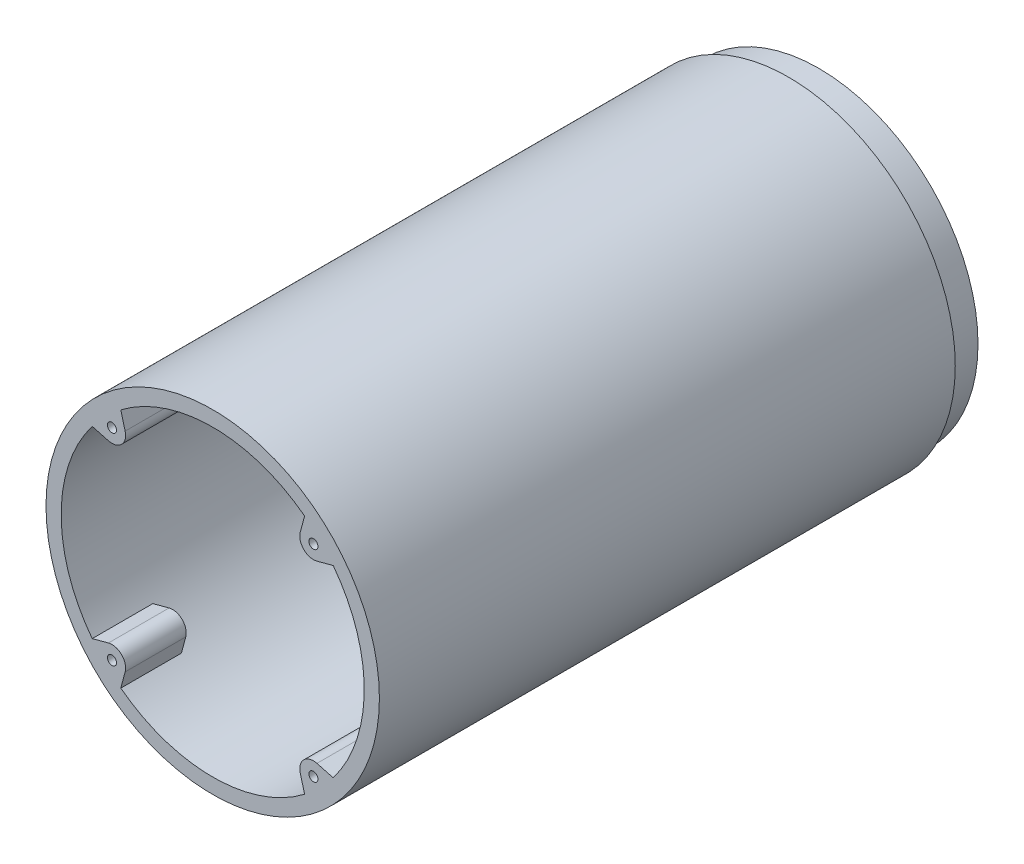
SolidWorks part; units mm, degrees
material "ABS"
ref_plane "前视基准面" through (0, 0, 0) normal (0, 0, 1) x (1, 0, 0)
ref_plane "上视基准面" through (0, 0, 0) normal (0, 1, 0) x (1, 0, 0)
ref_plane "右视基准面" through (0, 0, 0) normal (1, 0, 0) x (0, 0, -1)
sketch "草图2" plane through (0, 0, 0) normal (0, 0, 1) x (1, 0, 0)
  circle A0 centre (0, 0) radius 55
  circle A1 centre (0, 0) radius 50
  dimension "D1" = 100
  dimension "D2" = 110
extrude "凸台-拉伸1" add sketch "草图2" along normal blind 200
sketch "草图1" plane through (0, 0, 0) normal (0, 0, 1) x (1, 0, 0)
  line L0 (0, 0) -> (-25.5751, 0) construction
  line L1 (-49.5531, 6.6702) -> (-44.75, 3.8971)
  line L2 (-49.5531, -6.6702) -> (-44.75, -3.8971)
  line L3 (0, 0) -> (-6.6702, 49.5531) construction
  line L4 (-49.5531, -6.6702) -> (0, 0) construction
  line L5 (6.6702, 49.5531) -> (3.8971, 44.75)
  line L6 (-6.6702, 49.5531) -> (-3.8971, 44.75)
  line L7 (49.5531, -6.6702) -> (44.75, -3.8971)
  line L8 (49.5531, 6.6702) -> (44.75, 3.8971)
  line L9 (-6.6702, -49.5531) -> (-3.8971, -44.75)
  line L10 (6.6702, -49.5531) -> (3.8971, -44.75)
  circle A0 centre (0, 0) radius 50 construction
  circle A1 centre (0, 0) radius 55
  circle A2 centre (-47, 0) radius 1.5
  arc A4 (-44.75, 3.8971) -> (-44.75, -3.8971) centre (-47, 0) cw
  arc A5 (-49.5531, 6.6702) -> (-6.6702, 49.5531) centre (0, 0) cw
  circle A6 centre (0, 47) radius 1.5
  arc A7 (3.8971, 44.75) -> (-3.8971, 44.75) centre (0, 47) cw
  arc A8 (6.6702, 49.5531) -> (49.5531, 6.6702) centre (0, 0) cw
  circle A9 centre (47, 0) radius 1.5
  arc A10 (44.75, -3.8971) -> (44.75, 3.8971) centre (47, 0) cw
  arc A11 (49.5531, -6.6702) -> (6.6702, -49.5531) centre (0, 0) cw
  circle A12 centre (0, -47) radius 1.5
  arc A13 (-3.8971, -44.75) -> (3.8971, -44.75) centre (0, -47) cw
  arc A14 (-6.6702, -49.5531) -> (-49.5531, -6.6702) centre (0, 0) cw
  circle A15 centre (0, 0) radius 50 construction
  circle A16 centre (0, 0) radius 55 construction
  point P38 (0, 0)
  dimension "D3" = 47
  dimension "D4" = 3
  dimension "D5" = 3
  dimension "D7" = 90
  dimension "D8" = 4
  dimension "D6" = 30
extrude "凸台-拉伸2" add sketch "草图1" along normal blind 20 contours A1 A12 A9 A6 A2 L9 A14 L2 A4 L1 A5 L6 A7 L5 A8 L8 A10 L7 A11 L10 A13 region at (-53.4444, 0, 0)
sketch "草图3" plane through (0, 0, 20) normal (0, 0, 1) x (1, 0, 0)
  line L0 (-1.5877, 44.25) -> (1.5877, 44.25)
  line L1 (-44.25, -1.5877) -> (-44.25, 1.5877)
  line L2 (-44.25, 1.5877) -> (-47, 3.1754)
  line L3 (-47, 3.1754) -> (-49.75, 1.5877)
  line L4 (-49.75, 1.5877) -> (-49.75, -1.5877)
  line L5 (-49.75, -1.5877) -> (-47, -3.1754)
  line L6 (-47, -3.1754) -> (-44.25, -1.5877)
  line L7 (1.5877, 44.25) -> (3.1754, 47)
  line L8 (3.1754, 47) -> (1.5877, 49.75)
  line L9 (1.5877, 49.75) -> (-1.5877, 49.75)
  line L10 (-1.5877, 49.75) -> (-3.1754, 47)
  line L11 (-3.1754, 47) -> (-1.5877, 44.25)
  line L12 (44.25, 1.5877) -> (44.25, -1.5877)
  line L13 (44.25, -1.5877) -> (47, -3.1754)
  line L14 (47, -3.1754) -> (49.75, -1.5877)
  line L15 (49.75, -1.5877) -> (49.75, 1.5877)
  line L16 (49.75, 1.5877) -> (47, 3.1754)
  line L17 (47, 3.1754) -> (44.25, 1.5877)
  line L18 (1.5877, -44.25) -> (-1.5877, -44.25)
  line L19 (-1.5877, -44.25) -> (-3.1754, -47)
  line L20 (-3.1754, -47) -> (-1.5877, -49.75)
  line L21 (-1.5877, -49.75) -> (1.5877, -49.75)
  line L22 (1.5877, -49.75) -> (3.1754, -47)
  line L23 (3.1754, -47) -> (1.5877, -44.25)
  circle A0 centre (-47, 0) radius 2.75 construction
  circle A1 centre (0, 47) radius 2.75 construction
  circle A2 centre (47, 0) radius 2.75 construction
  circle A3 centre (0, -47) radius 2.75 construction
  point P36 (0, 0)
  dimension "D1" = 5.5
  dimension "D2" = 4
extrude "切除-拉伸1" cut sketch "草图3" against normal blind 2
ref_plane "基准面4" through (0, 0, 100) normal (0, 0, -1) x (-1, 0, 0)
sketch "草图4" plane through (0, 0, 0) normal (0, 0, -1) x (-1, 0, 0)
  circle A0 centre (0, 0) radius 55
  circle A1 centre (0, 0) radius 52.5
  circle A2 centre (0, 0) radius 55 construction
  dimension "D1" = 2.5
extrude "切除-拉伸2" cut sketch "草图4" against normal blind 10
sketch "草图5" plane through (0, 0, 0) normal (0, 0, 1) x (1, 0, 0)
  line L0 (0, 0) -> (-16.1279, 16.1279) construction
  line L1 (-30.3228, 39.7559) -> (-28.8874, 34.3987)
  line L2 (-39.7559, 30.3228) -> (-34.3987, 28.8874)
  line L3 (0, 0) -> (30.3228, 39.7559) construction
  line L4 (-39.7559, 30.3228) -> (0, 0) construction
  line L5 (39.7559, 30.3228) -> (34.3987, 28.8874)
  line L6 (30.3228, 39.7559) -> (28.8874, 34.3987)
  line L7 (30.3228, -39.7559) -> (28.8874, -34.3987)
  line L8 (39.7559, -30.3228) -> (34.3987, -28.8874)
  line L9 (-39.7559, -30.3228) -> (-34.3987, -28.8874)
  line L10 (-30.3228, -39.7559) -> (-28.8874, -34.3987)
  line L11 (0, 0) -> (-100.2667, 0) construction
  circle A0 centre (0, 0) radius 50 construction
  circle A1 centre (0, 0) radius 55
  circle A2 centre (-33.234, 33.234) radius 1.5
  arc A4 (-28.8874, 34.3987) -> (-34.3987, 28.8874) centre (-33.234, 33.234) cw
  arc A5 (-30.3228, 39.7559) -> (30.3228, 39.7559) centre (0, 0) cw
  circle A6 centre (33.234, 33.234) radius 1.5
  arc A7 (34.3987, 28.8874) -> (28.8874, 34.3987) centre (33.234, 33.234) cw
  arc A8 (39.7559, 30.3228) -> (39.7559, -30.3228) centre (0, 0) cw
  circle A9 centre (33.234, -33.234) radius 1.5
  arc A10 (28.8874, -34.3987) -> (34.3987, -28.8874) centre (33.234, -33.234) cw
  arc A11 (30.3228, -39.7559) -> (-30.3228, -39.7559) centre (0, 0) cw
  circle A12 centre (-33.234, -33.234) radius 1.5
  arc A13 (-34.3987, -28.8874) -> (-28.8874, -34.3987) centre (-33.234, -33.234) cw
  arc A14 (-39.7559, -30.3228) -> (-39.7559, 30.3228) centre (0, 0) cw
  point P38 (0, 0)
  dimension "D1" = 100
  dimension "D2" = 110
  dimension "D3" = 47
  dimension "D4" = 3
  dimension "D5" = 3
  dimension "D7" = 90
  dimension "D8" = 4
  dimension "D6" = 30
  dimension "D9" = 45
extrude "凸台-拉伸3" add sketch "草图5" against normal blind 20 from surface contours A1 A12 A9 A6 A2 L9 A14 L2 A4 L1 A5 L6 A7 L5 A8 L8 A10 L7 A11 L10 A13 region at (-53.4444, 0, 0) starting at face at (55, 0, 200)
sketch "草图6" plane through (0, 0, 0) normal (0, 0, 1) x (1, 0, 0)
  line L24 (0, 0) -> (-58.0423, 58.0423) construction
  line L25 (0, 0) -> (-90.9216, 0) construction
  line L26 (36.3012, 34.0559) -> (34.0559, 36.3012)
  line L27 (-34.0559, 36.3012) -> (-36.3012, 34.0559)
  line L28 (-36.3012, 34.0559) -> (-35.4794, 30.9887)
  line L29 (-35.4794, 30.9887) -> (-32.4122, 30.1668)
  line L30 (-32.4122, 30.1668) -> (-30.1668, 32.4122)
  line L31 (-30.1668, 32.4122) -> (-30.9887, 35.4794)
  line L32 (-30.9887, 35.4794) -> (-34.0559, 36.3012)
  line L33 (34.0559, 36.3012) -> (30.9887, 35.4794)
  line L34 (30.9887, 35.4794) -> (30.1668, 32.4122)
  line L35 (30.1668, 32.4122) -> (32.4122, 30.1668)
  line L36 (32.4122, 30.1668) -> (35.4794, 30.9887)
  line L37 (35.4794, 30.9887) -> (36.3012, 34.0559)
  line L38 (34.0559, -36.3012) -> (36.3012, -34.0559)
  line L39 (36.3012, -34.0559) -> (35.4794, -30.9887)
  line L40 (35.4794, -30.9887) -> (32.4122, -30.1668)
  line L41 (32.4122, -30.1668) -> (30.1668, -32.4122)
  line L42 (30.1668, -32.4122) -> (30.9887, -35.4794)
  line L43 (30.9887, -35.4794) -> (34.0559, -36.3012)
  line L44 (-36.3012, -34.0559) -> (-34.0559, -36.3012)
  line L45 (-34.0559, -36.3012) -> (-30.9887, -35.4794)
  line L46 (-30.9887, -35.4794) -> (-30.1668, -32.4122)
  line L47 (-30.1668, -32.4122) -> (-32.4122, -30.1668)
  line L48 (-32.4122, -30.1668) -> (-35.4794, -30.9887)
  line L49 (-35.4794, -30.9887) -> (-36.3012, -34.0559)
  circle A1 centre (-33.234, 33.234) radius 2.75 construction
  point P33 (0, 0)
  dimension "D1" = 45
  dimension "D3" = 4
  dimension "D2" = 5.5
extrude "切除-拉伸3" cut sketch "草图6" along normal blind 2.5 from surface starting at face at (-33.0224, -33.0224, 180)
